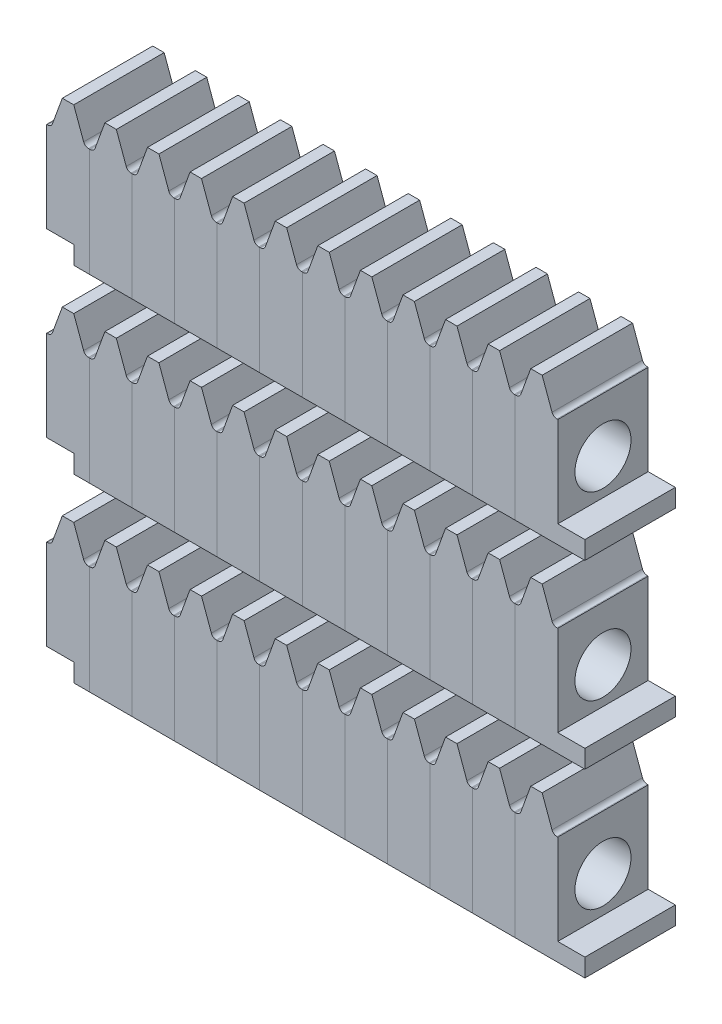
SolidWorks part; units mm, degrees
ref_plane "Front Plane" through (0, 0, 0) normal (0, 0, 1) x (1, 0, 0)
ref_plane "Top Plane" through (0, 0, 0) normal (0, 1, 0) x (1, 0, 0)
ref_plane "Right Plane" through (0, 0, 0) normal (1, 0, 0) x (0, 0, -1)
ref_axis "Axis1" through (0.1856, 0, 0) along (-1, 0, 0)
sketch "Sketch1" plane through (0, 0, 0) normal (0, 0, 1) x (1, 0, 0)
  line L0 (-3.7211, 0) -> (-2.4927, 3.375)
  line L1 (-2.4927, 3.375) -> (-1.2284, 3.375)
  line L2 (-1.2284, 3.375) -> (0, 0)
  line L3 (-3.7211, 0) -> (-4.7124, 0) construction
  line L4 (-3.7211, 0) -> (0, 0)
  line L5 (-3.5846, 0.375) -> (-4.8489, 0.375) construction
  line L6 (-4.7124, 0) -> (-5.3948, 1.875) construction
  line L7 (-5.3948, 1.875) -> (-0.6824, 1.875) construction
  dimension "D1" = 1.5
  dimension "D2" = 3.375
  dimension "D3" = 4.7124
  dimension "D4" = 3
  dimension "D5" = 70
  dimension "D6" = 0.9913
extrude "Main" add sketch "Sketch1" along normal blind 10
sketch "Sketch2" plane through (0, 0, 10) normal (0, 0, 1) x (1, 0, 0)
  line L1 (-4.2211, 0) -> (0.5, 0)
  line L2 (-4.2211, 0) -> (-4.2211, -12)
  line L3 (-4.2211, -12) -> (0.5, -12)
  line L4 (0.5, 0) -> (0.5, -12)
  line L6 (0.1856, 0) -> (-3.898, 0) construction
  point P12 (0, 0)
  dimension "D1" = 12
  dimension "D2" = 0.5
  dimension "D3" = 0.5
extrude "Support" add sketch "Sketch2" against normal up to surface (10 mm away) up to face at (-1.8605, 1.6875, 0)
sketch "Sketch3" plane through (-4.2211, 0, 0) normal (-1, 0, 0) x (0, 0, 1)
  line L0 (0, -12) -> (10, -12) construction
  line L1 (10, 0) -> (10, -12) construction
  circle A0 centre (5, -6) radius 3.1
  point P2 (5, -12)
  point P3 (10, -6)
  dimension "D1" = 6.2
extrude "AxisHole" cut sketch "Sketch3" against normal through all
fillet "Fillet1" radius 0.57 2 edges at (-3.7211, 0, 5) (0, 0, 5)
pattern_linear "LPattern2" count 12 spacing 4.71 along (-1, 0, 0) of bodies 112
sketch "Sketch4" plane through (0.5, 0, 0) normal (1, 0, 0) x (0, 0, -1)
  line L0 (-10, -12) -> (-10, 0) construction
  line L1 (-10, -10) -> (0, -10)
  line L2 (-10, -10) -> (-10, -12)
  line L3 (-10, -12) -> (0, -12)
  line L4 (0, -10) -> (0, -12)
  line L5 (0, -12) -> (-10, -12) construction
  line L6 (0, -12) -> (0, 0) construction
  dimension "D1" = 2
extrude "Boss-Extrude1" add sketch "Sketch4" along normal blind 3
sketch "Sketch5" plane through (-56.0311, 0, 0) normal (-1, 0, 0) x (0, 0, 1)
  line L0 (10, 0) -> (10, -12) construction
  line L1 (10, -10) -> (0, -10)
  line L2 (10, -10) -> (10, -12)
  line L3 (10, -12) -> (0, -12)
  line L4 (0, -10) -> (0, -12)
  dimension "D1" = 2
extrude "Cut-Extrude1" cut sketch "Sketch5" against normal blind 3
pattern_linear "LPattern3" count 3 spacing 20 along (0, -1, 0) of bodies 146 126 121 120 119 118 117 116 115 114 113 145
